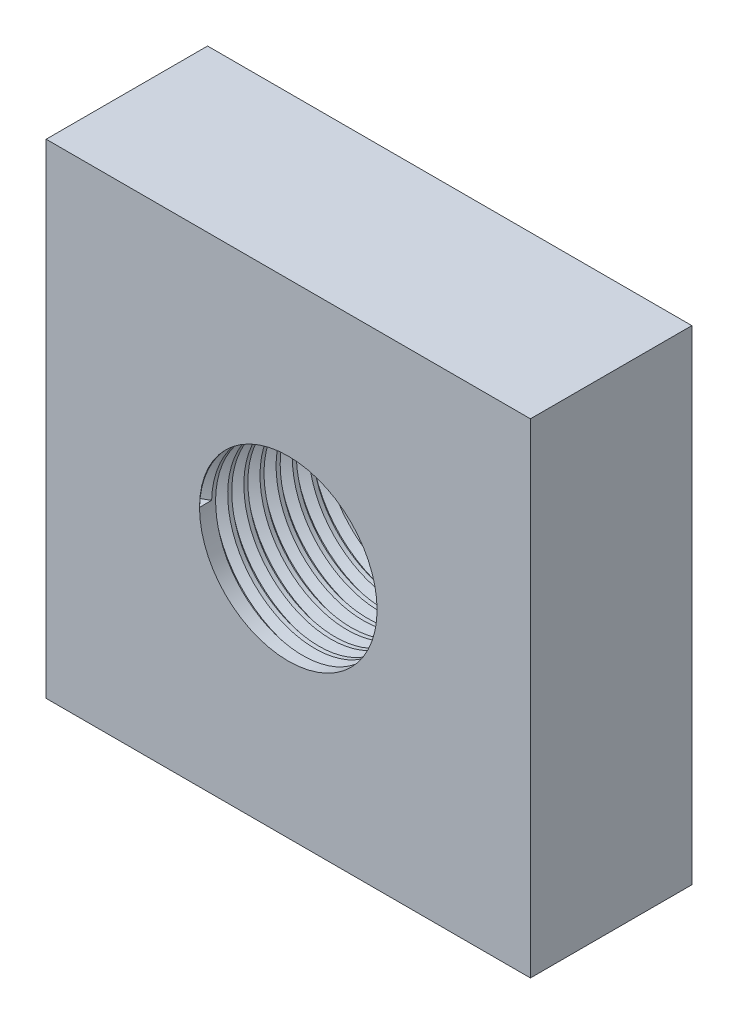
SolidWorks part; units mm, degrees
ref_plane "Piano frontale" through (0, 0, 0) normal (0, 0, 1) x (1, 0, 0)
ref_plane "Piano superiore" through (0, 0, 0) normal (0, 1, 0) x (1, 0, 0)
ref_plane "Piano destro" through (0, 0, 0) normal (1, 0, 0) x (0, 0, -1)
sketch "Schizzo1" plane through (0, 0, 0) normal (0, 0, 1) x (1, 0, 0)
  line L1 (-15, 15) -> (15, 15)
  line L2 (-15, 15) -> (-15, -15)
  line L3 (-15, -15) -> (15, -15)
  line L4 (15, 15) -> (15, -15)
  line L5 (-15, 15) -> (15, -15) construction
  line L6 (-15, -15) -> (15, 15) construction
  point P0 (0, 0)
  dimension "D1" = 30
extrude "Estrusione-Estrusione1" add sketch "Schizzo1" along normal blind 10
hole_wizard "Foro per Vite M10-1" positions "Schizzo3D2" profile "Schizzo3" hole size "M10" standard "BSI"
sketch3d "Schizzo3D2"
  line L0 (-15, -15, 10) -> (15, 15, 10) construction
  line L1 (15, -15, 10) -> (15, 15, 10) construction
  point P0 (0, 0, 10)
  point P9 (0, 0, 0)
sketch "Schizzo3" plane through (0, 0, 10) normal (1, 0, 0) x (0, -1, 0)
  line L0 (0, 0) -> (0, 18.3047)
  line L1 (0, 18.3047) -> (5.5, 15)
  line L2 (5.5, 15) -> (5.5, 0)
  line L5 (5.5, 0) -> (0, 0)
  line L10 (0, 18.3047) -> (-5.5, 15) construction
  line L11 (0, -6.35) -> (0, 107.95) construction
  dimension "Hole Dia." = 11
  dimension "Hole Depth" = 15
  dimension "Drill Angle" = 118
thread "Filettatura1" pitch 1 method cut profile "Profilo filettatura1" start angle 0, offset 0, length 10, pitch 1, diameter 11
ref_plane "Piano1" through (-5.5, 0, 10) normal (0, -1, 0) x (-1, 0, 0)
sketch "Profilo filettatura1" plane through (-5.5, 0, 10) normal (0, -1, 0) x (-1, 0, 0)
  line L0 (0, 0) -> (0, 1) construction
  line L1 (0, 0) -> (0.5413, 0.3125)
  line L2 (0.5413, 0.3125) -> (0.5413, 0.4375)
  line L3 (0.5413, 0.4375) -> (0, 0.75)
  line L4 (0.5413, 0.375) -> (0, 0.375) construction
  line L11 (0, 0) -> (0, 0.75)
  point P2 (0, 0)
  dimension "Pitch" = 1
  dimension "Profile_Angle" = 60
  dimension "Profile_Land" = 0.125
  dimension "Profile_Height" = 0.5413
